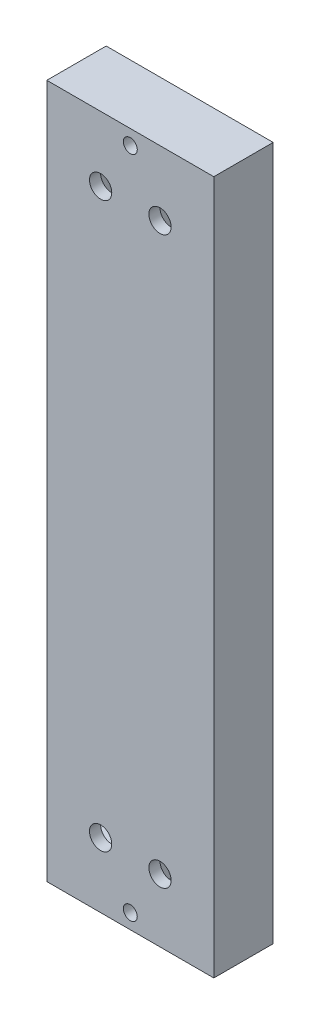
SolidWorks part; units mm, degrees
ref_plane "Front Plane" through (0, 0, 0) normal (0, 0, 1) x (1, 0, 0)
ref_plane "Top Plane" through (0, 0, 0) normal (0, 1, 0) x (1, 0, 0)
ref_plane "Right Plane" through (0, 0, 0) normal (1, 0, 0) x (0, 0, -1)
sketch "Sketch1" plane through (0, 0, 0) normal (0, 0, 1) x (1, 0, 0)
  line L1 (-6.5, -85.5) -> (6.5, -85.5)
  line L2 (-6.5, -85.5) -> (-6.5, 85.5)
  line L3 (-6.5, 85.5) -> (6.5, 85.5)
  line L4 (6.5, -85.5) -> (6.5, 85.5)
  line L5 (6.5, -84.5) -> (6.5, 84.5) construction
  line L6 (6.5, -85.5) -> (9.5, 85.5) construction
  line L7 (9.5, -85.5) -> (22.5, -85.5)
  line L8 (9.5, -85.5) -> (9.5, 85.5)
  line L9 (9.5, 85.5) -> (22.5, 85.5)
  line L10 (22.5, -85.5) -> (22.5, 85.5)
  line L11 (-14.5, -85.5) -> (30.5, -85.5)
  line L12 (-14.5, -93.5) -> (30.5, -93.5)
  line L13 (-14.5, -93.5) -> (-14.5, 93.5)
  line L14 (-14.5, 93.5) -> (30.5, 93.5)
  line L15 (30.5, -93.5) -> (30.5, 93.5)
  line L16 (-14.5, -93.5) -> (30.5, 93.5) construction
  line L17 (-14.5, 93.5) -> (30.5, -93.5) construction
  line L18 (-14.5, 85.5) -> (30.5, 85.5)
  line L19 (-12.5, -85.5) -> (-12.5, 85.5)
  line L20 (28.5, -85.5) -> (28.5, 85.5)
  line L21 (8, -93.5) -> (8, -85.5) construction
  line L22 (30.5, 0) -> (-14.5, 0) construction
  line L24 (-6.5, 84.5) -> (6.5, 84.5) construction
  line L25 (22.5, -84.5) -> (22.5, 84.5) construction
  line L26 (-6.5, -84.5) -> (-6.5, 84.5) construction
  line L27 (9.5, -84.5) -> (9.5, 84.5) construction
  line L28 (-6.5, -84.5) -> (6.5, -84.5) construction
  circle A0 centre (0, -76) radius 3
  circle A1 centre (16, -76.5) radius 3
  circle A2 centre (0, 76) radius 3
  circle A3 centre (16, 76) radius 3
  circle A4 centre (8, -89.5) radius 1.875
  circle A5 centre (8, 89.5) radius 1.875
  point P5 (-16.5, 86.5023)
  point P26 (8, 0)
  point P50 (-14.6077, -86.6347)
  point P53 (-14.5, -90.6692)
  point P56 (-14.5, -91.9118)
  point P59 (-14.5, -85.5)
  dimension "D3" = 3.75
  dimension "D1" = 8
  dimension "D2" = 8
  dimension "D4" = 2
  dimension "D5" = 2
  dimension "D6" = 1
  dimension "D7" = 1
extrude "Boss-Extrude1" add sketch "Sketch1" along normal blind 3 contours A2 | A3 | A0 | A1 | L13 L14 L15 L12 | A5 | A4 region at (0, -76, 0) region at (16, -76.5, 0) region at (0, 76, 0) region at (16, 76, 0)
extrude "Boss-Extrude2" add sketch "Sketch1<3>" against normal up to surface (13 mm away) contours L13 L18 L3 L9 L15 L14 A5 | L11 L19 L18 L13 | L12 L15 L11 L7 L1 L13 A4 | L20 L11 L15 L18 | L18 L4 L11 L8 region at (0, -85.9571, 0) region at (8, 0, 0) region at (-9.5, 85.9571, 0) region at (-13.5, 0, 0) region at (29.5, 0, 0)
sketch "Sketch1<3>" plane through (0, 0, 0) normal (0, 0, 1) x (1, 0, 0) same geometry as "Sketch1"
equation "\"D5@Sketch1\"=\"D4@Sketch1\""
